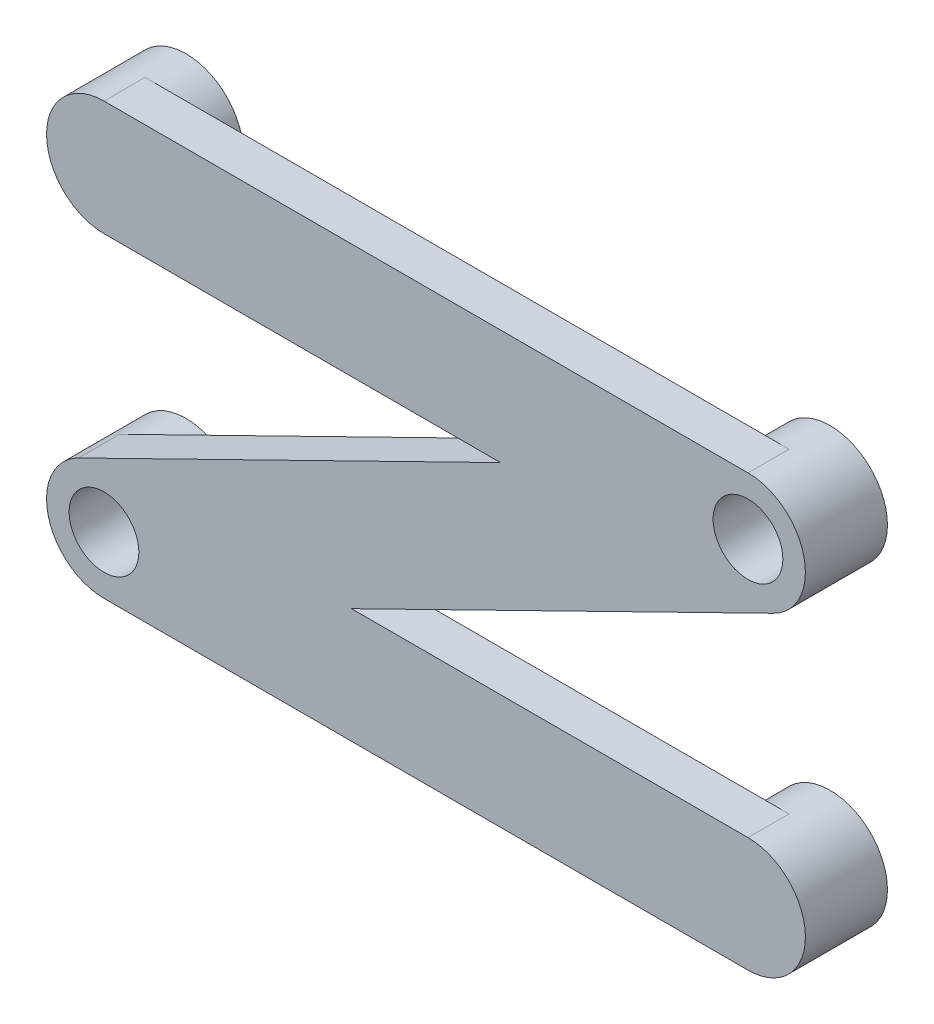
SolidWorks part; units mm, degrees
ref_plane "Спереди" through (0, 0, 0) normal (0, 0, 1) x (1, 0, 0)
ref_plane "Сверху" through (0, 0, 0) normal (0, 1, 0) x (1, 0, 0)
ref_plane "Справа" through (0, 0, 0) normal (1, 0, 0) x (0, 0, -1)
sketch "Эскиз1" plane through (0, 0, 0) normal (0, 0, 1) x (1, 0, 0)
  line L0 (-15.7, 10.5) -> (15.7, 10.5)
  line L5 (-15.7, 7.7) -> (15.7, 7.7) construction
  line L6 (-15.7, 7.7) -> (-15.7, -7.7) construction
  line L7 (-15.7, -7.7) -> (15.7, -7.7) construction
  line L8 (15.7, 7.7) -> (15.7, -7.7) construction
  line L9 (-15.7, 7.7) -> (15.7, -7.7) construction
  line L10 (-15.7, -7.7) -> (15.7, 7.7) construction
  line L11 (-15.7, 4.9) -> (3.6322, 4.9)
  line L12 (-3.6322, -4.9) -> (15.7, -4.9)
  line L13 (16.9329, 5.1861) -> (-3.6322, -4.9)
  line L14 (-15.7, -10.5) -> (15.7, -10.5)
  line L15 (3.6322, 4.9) -> (-16.9329, -5.1861)
  circle A0 centre (15.7, 7.7) radius 2.8
  circle A1 centre (15.7, -7.7) radius 2.8
  circle A2 centre (-15.7, -7.7) radius 2.8
  circle A3 centre (-15.7, 7.7) radius 2.8
  circle A8 centre (15.7, 7.7) radius 1.7
  circle A9 centre (-15.7, -7.7) radius 1.7
  point P4 (0, 0)
  dimension "D3" = 5.6
  dimension "D4" = 3.4
  dimension "D1" = 31.4
  dimension "D2" = 15.4
extrude "Основа" add sketch "Эскиз1" against normal blind 2 contours A3 L11 L15 A2 L14 A1 L12 L13 A0 L0 region at (0, 0, 0)
extrude "Стойки" add sketch "Эскиз1<5>" against normal blind 4 contours A3 | A0 | A1 | A2 region at (-15.7, 7.7, 0) region at (17.6239, 9.6239, 0) region at (-14.2607, -5.3911, 0) region at (15.7, -7.7, 0)
sketch "Эскиз1<5>" plane through (0, 0, 0) normal (0, 0, 1) x (1, 0, 0) same geometry as "Эскиз1"
